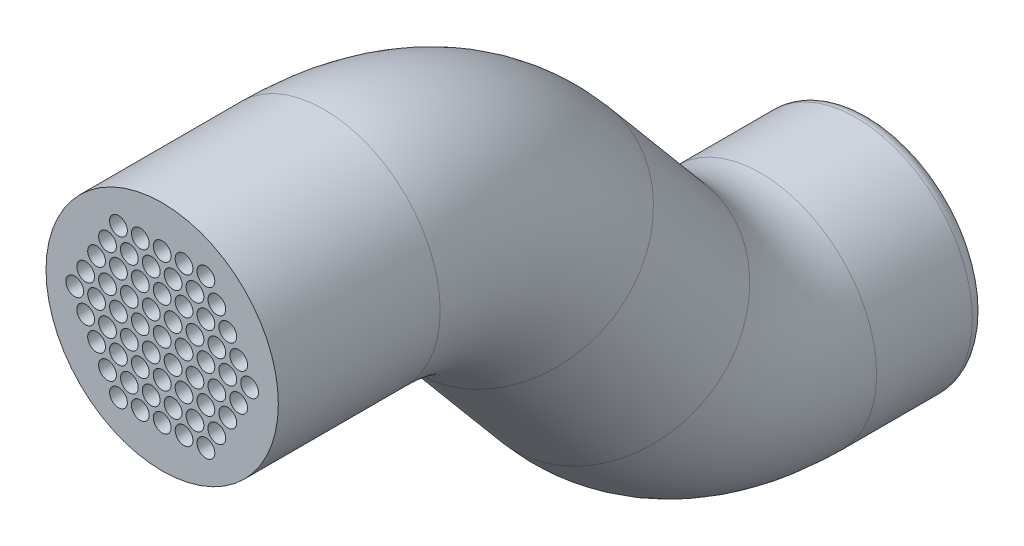
SolidWorks part; units mm, degrees
ref_plane "Спереди" through (0, 0, 0) normal (0, 0, 1) x (1, 0, 0)
ref_plane "Сверху" through (0, 0, 0) normal (0, 1, 0) x (1, 0, 0)
ref_plane "Справа" through (0, 0, 0) normal (1, 0, 0) x (0, 0, -1)
sketch "Sketch1" plane through (0, 0, 0) normal (0, 0, 1) x (1, 0, 0)
  circle B0 centre (-6.4, 10.88) radius 1.3
  circle B1 centre (-3.2, 10.88) radius 1.3
  circle B2 centre (0, 10.88) radius 1.3
  circle B3 centre (3.2, 10.88) radius 1.3
  circle B4 centre (6.4, 10.88) radius 1.3
  circle B5 centre (-9.6, 5.44) radius 1.3
  circle B6 centre (-6.4, 5.44) radius 1.3
  circle B7 centre (-3.2, 5.44) radius 1.3
  circle B8 centre (0, 5.44) radius 1.3
  circle B9 centre (3.2, 5.44) radius 1.3
  circle B10 centre (6.4, 5.44) radius 1.3
  circle B11 centre (9.6, 5.44) radius 1.3
  circle B12 centre (-12.8, 0) radius 1.3
  circle B13 centre (-9.6, 0) radius 1.3
  circle B14 centre (-6.4, 0) radius 1.3
  circle B15 centre (-3.2, 0) radius 1.3
  circle B16 centre (0, 0) radius 1.3
  circle B17 centre (3.2, 0) radius 1.3
  circle B18 centre (6.4, 0) radius 1.3
  circle B19 centre (9.6, 0) radius 1.3
  circle B20 centre (-9.6, -5.44) radius 1.3
  circle B21 centre (-6.4, -5.44) radius 1.3
  circle B22 centre (-3.2, -5.44) radius 1.3
  circle B23 centre (0, -5.44) radius 1.3
  circle B24 centre (3.2, -5.44) radius 1.3
  circle B25 centre (6.4, -5.44) radius 1.3
  circle B26 centre (9.6, -5.44) radius 1.3
  circle B27 centre (-8, 8.1087) radius 1.3
  circle B28 centre (-4.8, 8.1087) radius 1.3
  circle B29 centre (-1.6, 8.1087) radius 1.3
  circle B30 centre (1.6, 8.1087) radius 1.3
  circle B31 centre (4.8, 8.1087) radius 1.3
  circle B32 centre (8, 8.1087) radius 1.3
  circle B33 centre (-11.2, 2.6687) radius 1.3
  circle B34 centre (-8, 2.6687) radius 1.3
  circle B35 centre (-4.8, 2.6687) radius 1.3
  circle B36 centre (-1.6, 2.6687) radius 1.3
  circle B37 centre (1.6, 2.6687) radius 1.3
  circle B38 centre (4.8, 2.6687) radius 1.3
  circle B39 centre (8, 2.6687) radius 1.3
  circle B40 centre (-11.2, -2.7713) radius 1.3
  circle B41 centre (-8, -2.7713) radius 1.3
  circle B42 centre (-4.8, -2.7713) radius 1.3
  circle B43 centre (-1.6, -2.7713) radius 1.3
  circle B44 centre (1.6, -2.7713) radius 1.3
  circle B45 centre (4.8, -2.7713) radius 1.3
  circle B46 centre (8, -2.7713) radius 1.3
  circle B47 centre (-8, -8.2113) radius 1.3
  circle B48 centre (-4.8, -8.2113) radius 1.3
  circle B49 centre (-1.6, -8.2113) radius 1.3
  circle B50 centre (1.6, -8.2113) radius 1.3
  circle B51 centre (4.8, -8.2113) radius 1.3
  circle B52 centre (8, -8.2113) radius 1.3
  circle B53 centre (12.8, 0) radius 1.3
  circle B54 centre (11.2, 2.6687) radius 1.3
  circle B55 centre (11.2, -2.7713) radius 1.3
  circle B56 centre (-6.4, -10.88) radius 1.3
  circle B57 centre (-3.2, -10.88) radius 1.3
  circle B58 centre (0, -10.88) radius 1.3
  circle B59 centre (3.2, -10.88) radius 1.3
  circle B60 centre (6.4, -10.88) radius 1.3
  circle B61 centre (0, 0) radius 17
sketch_block_instance "Block1-1"
sketch_block "Block1" parameters "D1"=2.6, "D2"=34
sketch "Sketch2" plane through (0, 0, 0) normal (1, 0, 0) x (0, 0, -1)
  line L0 (0, 0) -> (23.6792, 0)
  line L1 (50.4908, -12.5024) -> (64.5719, -29.2836)
  line L2 (87.5532, -40) -> (103.564, -40)
  arc A0 (50.4908, -12.5024) -> (23.6792, 0) centre (23.6792, -35) ccw
  arc A1 (87.5532, -40) -> (64.5719, -29.2836) centre (87.5532, -10) cw
  point P7 (40, 0)
  point P10 (73.564, -40)
  dimension "D5" = 35
  dimension "D6" = 30
  dimension "D1" = 40
  dimension "D2" = 40
  dimension "D3" = 130
  dimension "D4" = 30
sweep "Sweep1" add profiles "Sketch1" path "Sketch2"
sketch "Sketch4" plane through (0, 0, 0) normal (1, 0, 0) x (0, 0, -1)
  line L1 (-15.7593, 28.4605) -> (109.5456, 28.4605)
  line L2 (-15.7593, 28.4605) -> (-15.7593, -73.3065)
  line L3 (-15.7593, -73.3065) -> (109.5456, -73.3065)
  line L4 (109.5456, 28.4605) -> (109.5456, -73.3065)
extrude "Cut-Extrude1" [suppressed] cut sketch "Sketch4" along normal blind 20 and the other way blind 8
fillet "Fillet1" radius 2 1 edges at (17, -40, -103.564)
sketch "Sketch5" plane through (0, 0, 0) normal (0, 0, 1) x (1, 0, 0)
  circle A0 centre (0, 0) radius 14
  dimension "D1" = 28
